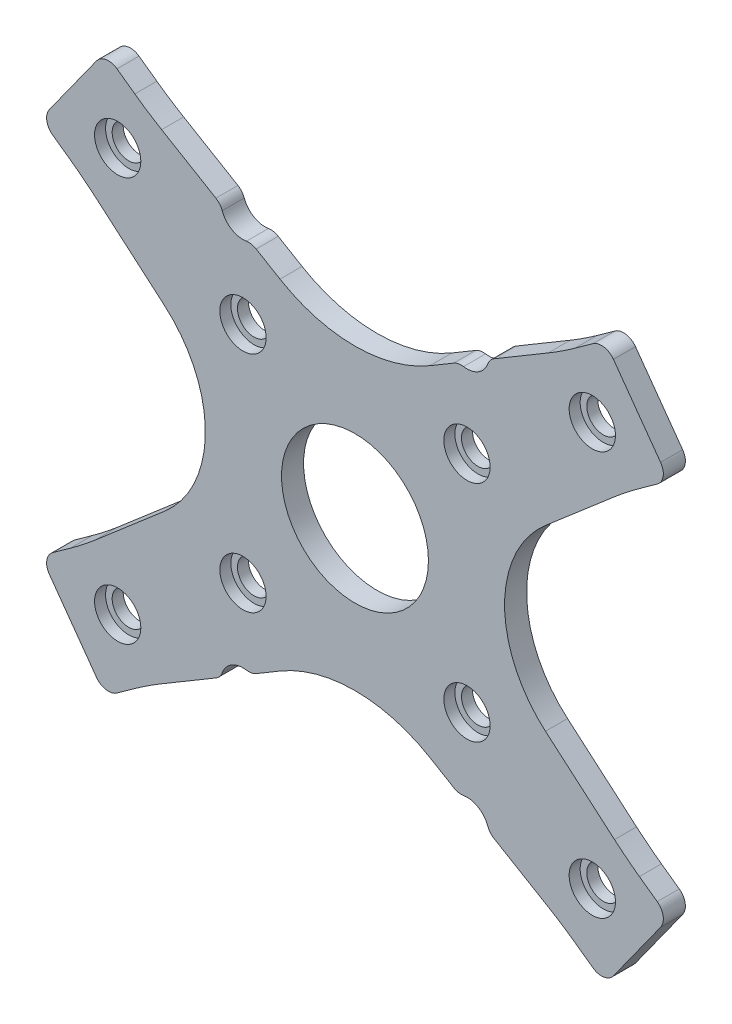
SolidWorks part; units mm, degrees
material "Thornel Mat VMA"
ref_plane "Front Plane" through (0, 0, 0) normal (0, 0, 1) x (1, 0, 0)
ref_plane "Top Plane" through (0, 0, 0) normal (0, 1, 0) x (1, 0, 0)
ref_plane "Right Plane" through (0, 0, 0) normal (1, 0, 0) x (0, 0, -1)
sketch "Sketch2" plane through (0, 0, 0) normal (0, 0, 1) x (1, 0, 0)
  line L4 (-13.4504, 25.0311) -> (-10.205, 23.1057)
  line L5 (10.205, 23.1057) -> (13.4504, 25.0311)
  line L6 (18.9376, 28.2867) -> (26.3219, 32.6678)
  line L7 (29.9727, 35.055) -> (32.401, 36.7987)
  line L8 (35.1921, 36.3406) -> (41.608, 27.4055)
  line L9 (41.15, 24.6144) -> (38.7216, 22.8708)
  line L10 (35.3286, 20.2052) -> (25.9268, 12.1239)
  line L11 (25.9382, -12.1337) -> (35.3286, -20.2052)
  line L12 (38.7216, -22.8708) -> (41.15, -24.6144)
  line L13 (41.608, -27.4055) -> (35.1921, -36.3406)
  line L14 (32.401, -36.7986) -> (29.9727, -35.055)
  line L15 (26.3219, -32.6678) -> (18.9376, -28.2867)
  line L16 (13.4504, -25.0311) -> (10.2058, -23.1061)
  line L17 (-10.205, -23.1057) -> (-13.4504, -25.0311)
  line L26 (0, 0) -> (0, -50000) construction
  line L27 (-26.3219, -32.6678) -> (-18.9376, -28.2867)
  line L28 (-32.401, -36.7986) -> (-29.9727, -35.055)
  line L29 (-41.608, -27.4055) -> (-35.1921, -36.3406)
  line L30 (-38.7216, -22.8708) -> (-41.15, -24.6144)
  line L31 (-25.9382, -12.1337) -> (-35.3286, -20.2052)
  line L32 (-35.3286, 20.2052) -> (-25.9268, 12.1239)
  line L33 (-41.15, 24.6144) -> (-38.7216, 22.8708)
  line L34 (-35.1921, 36.3406) -> (-41.608, 27.4055)
  line L35 (-29.9727, 35.055) -> (-32.401, 36.7987)
  line L36 (-18.9376, 28.2867) -> (-26.3219, 32.6678)
  circle A0 centre (0, 0) radius 10
  arc A23 (-13.4504, 25.0311) -> (-14.7825, 25.2866) centre (-14.4709, 23.3111) ccw
  arc A24 (-10.205, 23.1057) -> (10.205, 23.1057) centre (0, 40.3062) ccw
  arc A25 (14.7825, 25.2866) -> (13.4504, 25.0311) centre (14.4709, 23.3111) ccw
  arc A26 (14.7825, 25.2866) -> (18.0749, 27.24) centre (15.25, 28.25) ccw
  arc A27 (18.9376, 28.2867) -> (18.0749, 27.24) centre (19.9581, 26.5666) ccw
  arc A28 (26.3219, 32.6678) -> (29.9727, 35.055) centre (0.8094, 75.6691) ccw
  arc A29 (35.1921, 36.3406) -> (32.401, 36.7987) centre (33.5675, 35.1741) ccw
  arc A30 (41.15, 24.6144) -> (41.608, 27.4055) centre (39.9834, 26.239) ccw
  arc A31 (38.7216, 22.8708) -> (35.3286, 20.2052) centre (67.8849, -17.7434) ccw
  arc A32 (25.9268, 12.1239) -> (25.9382, -12.1337) centre (36.3676, 0) ccw
  arc A33 (35.3286, -20.2052) -> (38.7216, -22.8708) centre (67.8849, 17.7434) ccw
  arc A34 (41.608, -27.4055) -> (41.15, -24.6144) centre (39.9834, -26.239) ccw
  arc A35 (32.401, -36.7986) -> (35.1921, -36.3406) centre (33.5675, -35.1741) ccw
  arc A36 (29.9727, -35.055) -> (26.3219, -32.6678) centre (0.8094, -75.6691) ccw
  arc A37 (18.0749, -27.24) -> (18.9376, -28.2867) centre (19.9581, -26.5666) ccw
  arc A38 (18.0749, -27.24) -> (14.7825, -25.2866) centre (15.25, -28.25) ccw
  arc A39 (13.4504, -25.0311) -> (14.7825, -25.2866) centre (14.4709, -23.3111) ccw
  arc A40 (10.2058, -23.1061) -> (-10.205, -23.1057) centre (0, -40.3062) ccw
  arc A41 (-14.7825, -25.2866) -> (-13.4504, -25.0311) centre (-14.4709, -23.3111) ccw
  arc A88 (-18.0749, -27.24) -> (-14.7825, -25.2866) centre (-15.25, -28.25) cw
  arc A89 (-18.0749, -27.24) -> (-18.9376, -28.2867) centre (-19.9581, -26.5666) cw
  arc A90 (-29.9727, -35.055) -> (-26.3219, -32.6678) centre (-0.8094, -75.6691) cw
  arc A91 (-32.401, -36.7986) -> (-35.1921, -36.3406) centre (-33.5675, -35.1741) cw
  arc A92 (-41.608, -27.4055) -> (-41.15, -24.6144) centre (-39.9834, -26.239) cw
  arc A93 (-35.3286, -20.2052) -> (-38.7216, -22.8708) centre (-67.8849, 17.7433) cw
  arc A94 (-25.9268, 12.1239) -> (-25.9382, -12.1337) centre (-36.3677, 0) cw
  arc A95 (-38.7216, 22.8708) -> (-35.3286, 20.2052) centre (-67.8849, -17.7433) cw
  arc A96 (-41.15, 24.6144) -> (-41.608, 27.4055) centre (-39.9834, 26.239) cw
  arc A97 (-35.1921, 36.3406) -> (-32.401, 36.7987) centre (-33.5675, 35.1741) cw
  arc A98 (-26.3219, 32.6678) -> (-29.9727, 35.055) centre (-0.8094, 75.6691) cw
  arc A99 (-18.9376, 28.2867) -> (-18.0749, 27.24) centre (-19.9581, 26.5666) cw
  arc A100 (-14.7825, 25.2866) -> (-18.0749, 27.24) centre (-15.25, 28.25) cw
  dimension "D1" = 20
extrude "Boss-Extrude1" add sketch "Sketch2" along normal blind 3
hole_wizard "CBORE for M4 SHCS1" positions "Sketch3" profile "Sketch4" counterbore size "M4" standard "ANSI Metric" end condition up to next
sketch "Sketch3" plane through (0, 0, 3) normal (0, 0, 1) x (1, 0, 0)
  line L0 (0, 4.2996) -> (-32.3079, 27.4986) construction
  line L4 (0, -4.2996) -> (0, 4.2996) construction
  line L5 (-32.3079, -27.4986) -> (0, -4.2996) construction
  point P0 (-32.3079, 27.4986)
  point P3 (-15.25, 15.25)
  point P6 (-15.25, -15.25)
  point P9 (-32.3079, -27.4986)
  point P55 (15.25, 15.25)
  point P56 (32.3079, 27.4986)
  point P68 (32.3079, -27.4986)
  point P69 (15.25, -15.25)
  dimension "D1" = 21
  dimension "D2" = 21
  dimension "D3" = 18.7743
  dimension "D4" = 125.681
  dimension "D5" = 8.5992
  dimension "D6" = 18.7743
  dimension "D7" = 125.681
sketch "Sketch4" plane through (-32.3079, 27.4986, 3) normal (1, 0, 0) x (0, -1, 0)
  line L0 (0, 0) -> (0, 3)
  line L1 (0, 3) -> (2.25, 3)
  line L3 (2.25, 3) -> (2.25, 1.5)
  line L4 (2.25, 1.5) -> (3.15, 1.5)
  line L5 (3.15, 1.5) -> (3.15, 0)
  line L7 (3.15, 0) -> (0, 0)
  line L11 (0, -6.35) -> (0, 107.95) construction
  dimension "Thru Hole Dia." = 4.5
  dimension "Thru Hole Depth" = 3
  dimension "C'Bore Dia." = 6.3
  dimension "C'Bore Depth" = 1.5
